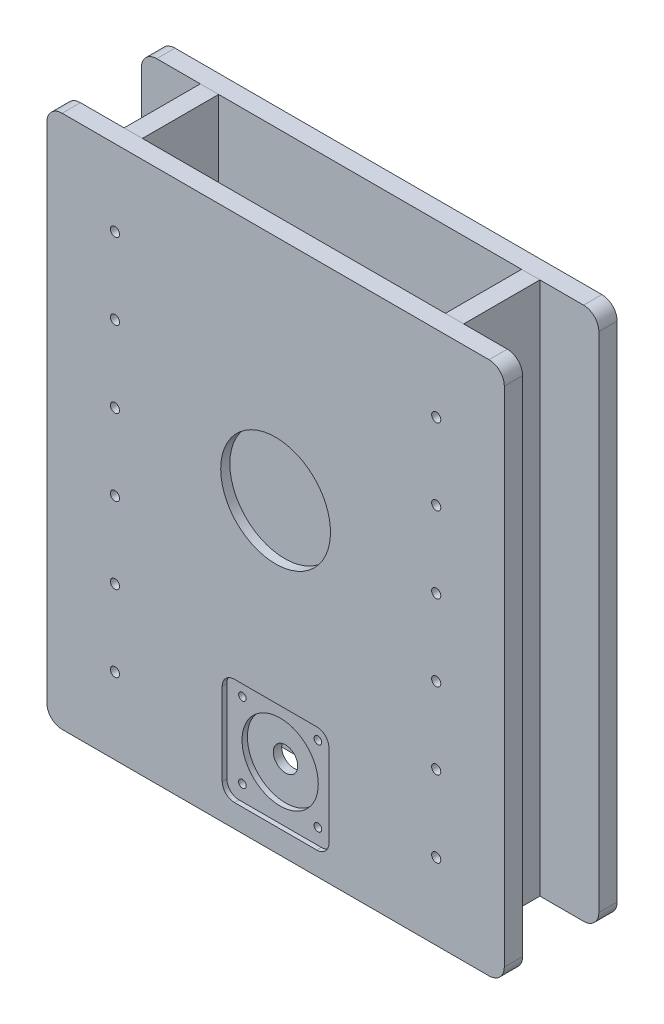
SolidWorks part; units mm, degrees
material "6061 Alloy"
ref_plane "Front Plane" through (0, 0, 0) normal (1, 0, 0) x (0, 1, 0)
ref_plane "Top Plane" through (0, 0, 0) normal (0, 0, 1) x (0, 1, 0)
ref_plane "Right Plane" through (0, 0, 0) normal (0, 1, 0) x (-1, 0, 0)
sketch "Sketch1" plane through (0, 0, 0) normal (0, 0, 1) x (0, 1, 0)
  line L1 (-150, 150) -> (150, 150)
  line L2 (-150, 150) -> (-150, -150)
  line L3 (-150, -150) -> (150, -150)
  line L4 (150, 150) -> (150, -150)
  line L5 (-150, 150) -> (150, -150) construction
  line L6 (-150, -150) -> (150, 150) construction
  point P1 (0, 0)
  dimension "D1" = 300
extrude "Boss-Extrude1" add sketch "Sketch1" along normal blind 12
sketch "Sketch2" plane through (0, 0, 0) normal (0, 0, -1) x (-1, 0, 0)
  circle A0 centre (0, 0) radius 45
  dimension "D1" = 90
extrude "Cut-Extrude1" cut sketch "Sketch2" against normal blind 6
sketch "Sketch3" plane through (0, 0, 6) normal (0, 0, -1) x (1, 0, 0)
  circle A0 centre (0, 0) radius 36
  dimension "D1" = 72
extrude "Cut-Extrude2" cut sketch "Sketch3" against normal blind 6
sketch "Sketch4" plane through (0, 0, 12) normal (0, 0, 1) x (1, 0, 0)
  line L0 (150, -150) -> (150, 150) construction
  line L1 (-150, -150) -> (150, -150)
  line L2 (-150, -150) -> (-150, -200)
  line L3 (-150, -200) -> (150, -200)
  line L4 (150, -150) -> (150, -200)
  line L5 (-150, -150) -> (150, -200) construction
  line L6 (-150, -200) -> (150, -150) construction
  point P4 (0, -175)
  dimension "D1" = 50
extrude "Boss-Extrude2" add sketch "Sketch4" against normal blind 12
sketch "Sketch6" plane through (0, 0, 12) normal (0, 0, 1) x (1, 0, 0)
  line L0 (0, -6.6) -> (0, 6.6) construction
  line L1 (6.6, 0) -> (-6.6, 0) construction
  line L2 (-35, -115) -> (35, -115)
  line L3 (-35, -115) -> (-35, -185)
  line L4 (-35, -185) -> (35, -185)
  line L5 (35, -115) -> (35, -185)
  line L6 (-35, -115) -> (35, -185) construction
  line L7 (-35, -185) -> (35, -115) construction
  circle A0 centre (0, -150) radius 25
  circle A1 centre (0, -150) radius 35 construction
  circle A2 centre (0, -150) radius 8
  circle A3 centre (-24.7487, -125.2513) radius 2.5
  circle A4 centre (24.7487, -125.2513) radius 2.5
  circle A5 centre (24.7487, -174.7487) radius 2.5
  circle A6 centre (-24.7487, -174.7487) radius 2.5
  dimension "D1" = 50
  dimension "D2" = 70
  dimension "D4" = 16
  dimension "D5" = 5
  dimension "D3" = 70
  dimension "D7" = 150
  dimension "D6" = 4
extrude "Cut-Extrude3" cut sketch "Sketch6" against normal blind 12 contours A3 | A4 | A2 | A5 | A6 region at (0, -150, 12) region at (-24.7487, -125.2513, 12) region at (24.7487, -125.2513, 12) region at (24.7487, -174.7487, 12) region at (-24.7487, -174.7487, 12)
extrude "Cut-Extrude4" cut sketch "Sketch6<3>" against normal blind 6.5 contours A0
sketch "Sketch6<3>" plane through (0, 0, 12) normal (0, 0, 1) x (1, 0, 0) same geometry as "Sketch6"
extrude "Cut-Extrude5" cut sketch "Sketch6<4>" against normal blind 3 contours L2 L5 L4 L3
sketch "Sketch6<4>" plane through (0, 0, 12) normal (0, 0, 1) x (1, 0, 0) same geometry as "Sketch6"
fillet "Fillet1" radius 8 4 edges at (35, -185, 10.5) (-35, -185, 10.5) (-35, -115, 10.5) (35, -115, 10.5)
sketch "Sketch7" plane through (0, 0, 12) normal (0, 0, 1) x (1, 0, 0)
  line L0 (-105.3527, 150) -> (-105.3527, -200) construction
  line L1 (150, 150) -> (-150, 150) construction
  line L2 (-150, -200) -> (150, -200) construction
  line L3 (0, -6.6) -> (0, 6.6) construction
  line L8 (150, 150) -> (-150, 150)
  line L9 (-150, 150) -> (-150, -200)
  line L10 (-150, -200) -> (150, -200)
  line L11 (150, -200) -> (150, 150)
  line L12 (150, 150) -> (-150, 150)
  line L13 (-150, 150) -> (-150, -200)
  line L14 (-150, -200) -> (150, -200)
  line L15 (150, -200) -> (150, 150)
  circle A0 centre (-105.3527, 0) radius 3
  circle A1 centre (-105.3527, -50) radius 3
  circle A2 centre (-105.3527, -100) radius 3
  circle A3 centre (-105.3527, -150) radius 3
  circle A4 centre (-105.3527, 50) radius 3
  circle A5 centre (-105.3527, 100) radius 3
  circle A6 centre (105.3527, -150) radius 3
  circle A7 centre (105.3527, -100) radius 3
  circle A8 centre (105.3527, -50) radius 3
  circle A9 centre (105.3527, 0) radius 3
  circle A10 centre (105.3527, 50) radius 3
  circle A11 centre (105.3527, 100) radius 3
  dimension "D1" = 6
  dimension "D4" = 0
  dimension "D2" = 4
  dimension "D3" = 3
extrude "Cut-Extrude6" cut sketch "Sketch7" against normal through all both and the other way through all contours A5 | A4 | A0 | A1 | A2 | A3 | A6 | A7 | A8 | A9 | A10 | A11
sketch "Sketch8" plane through (0, 0, 0) normal (0, 0, -1) x (1, 0, 0)
  line L0 (-105.3527, -150) -> (-105.3527, 200) construction
  line L1 (150, -150) -> (-150, -150) construction
  line L2 (-150, 200) -> (150, 200) construction
  line L3 (0, -6.6) -> (0, 6.6) construction
  line L4 (-111.3527, 200) -> (-99.3527, 200)
  line L5 (-111.3527, 200) -> (-111.3527, -150)
  line L6 (-111.3527, -150) -> (-99.3527, -150)
  line L7 (-99.3527, 200) -> (-99.3527, -150)
  line L8 (-111.3527, 200) -> (-99.3527, -150) construction
  line L9 (-111.3527, -150) -> (-99.3527, 200) construction
  line L10 (111.3527, -150) -> (99.3527, -150)
  line L11 (99.3527, 200) -> (99.3527, -150)
  line L12 (111.3527, 200) -> (99.3527, 200)
  line L13 (111.3527, 200) -> (111.3527, -150)
  line L14 (111.3527, -150) -> (99.3527, 200) construction
  line L15 (111.3527, 200) -> (99.3527, -150) construction
  circle A0 centre (-105.3527, -100) radius 3 construction
  circle A1 centre (-105.3527, -100) radius 3
  point P9 (-105.3527, 25)
  point P20 (105.3527, 25)
  dimension "D1" = 350
  dimension "D2" = 12
extrude "Boss-Extrude3" add sketch "Sketch8" along normal blind 50 separate body
sketch "Sketch9" plane through (0, 0, -50) normal (0, 0, -1) x (1, 0, 0)
  line L4 (-150, -150) -> (150, -150)
  line L5 (150, -150) -> (150, 200)
  line L6 (150, 200) -> (-150, 200)
  line L7 (-150, 200) -> (-150, -150)
  line L8 (-150, -150) -> (150, -150)
  line L9 (150, -150) -> (150, 200)
  line L10 (150, 200) -> (-150, 200)
  line L11 (-150, 200) -> (-150, -150)
  dimension "D1" = 0
extrude "Boss-Extrude4" add sketch "Sketch9" along normal blind 12 separate body
fillet "Fillet2" radius 10 4 edges at (150, 150, 6) (150, -200, 6) (-150, 150, 6) (-150, -200, 6)
fillet "Fillet3" radius 10 4 edges at (-150, -200, -56) (150, -200, -56) (-150, 150, -56) (150, 150, -56)
